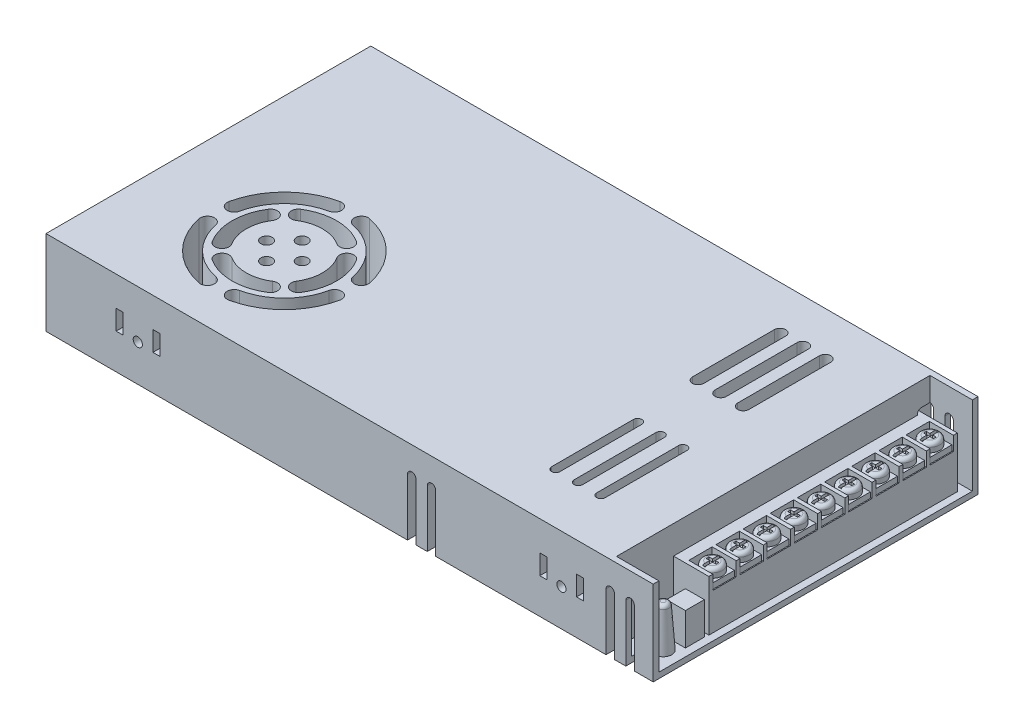
SolidWorks part; units mm, degrees
material "aluminio"
ref_plane "Alzado" through (0, 0, 0) normal (0, 0, 1) x (1, 0, 0)
ref_plane "Planta" through (0, 0, 0) normal (0, 1, 0) x (1, 0, 0)
ref_plane "Vista lateral" through (0, 0, 0) normal (1, 0, 0) x (0, 0, -1)
sketch "Croquis1" plane through (0, 0, 0) normal (0, 1, 0) x (1, 0, 0)
  line L1 (0, 0) -> (215, 0)
  line L2 (0, 0) -> (0, 115)
  line L3 (0, 115) -> (215, 115)
  line L4 (215, 0) -> (215, 115)
  dimension "D1" = 215
  dimension "D2" = 115
extrude "Saliente-Extruir1" add sketch "Croquis1" along normal blind 30
sketch "Croquis2" plane through (0, 30, 0) normal (0, 1, 0) x (1, 0, 0)
  line L0 (215, 0) -> (215, 115) construction
  line L1 (215, 113) -> (200, 113)
  line L2 (215, 113) -> (215, 2)
  line L3 (215, 2) -> (200, 2)
  line L4 (200, 113) -> (200, 2)
  line L5 (215, 115) -> (0, 115) construction
  line L6 (0, 115) -> (0, 0) construction
  line L7 (0, 0) -> (215, 0) construction
  dimension "D1" = 2
  dimension "D2" = 2
  dimension "D3" = 200
extrude "Cortar-Extruir1" cut sketch "Croquis2" against normal offset from surface (28 mm away) 2 up to face at (107.5, 0, -57.5)
sketch "Croquis7" plane through (0, 30, 0) normal (0, 1, 0) x (1, 0, 0)
  line L0 (176.4, 99.5) -> (176.4, 70.5) construction
  line L1 (178.4, 99.5) -> (178.4, 70.5)
  line L2 (174.4, 99.5) -> (174.4, 70.5)
  line L3 (200, 113) -> (200, 2) construction
  line L4 (178.5, 47) -> (178.5, 18) construction
  line L5 (180, 47) -> (180, 18)
  line L6 (177, 47) -> (177, 18)
  line L7 (0, 0) -> (215, 0) construction
  line L8 (215, 115) -> (0, 115) construction
  line L9 (168.4, 99.5) -> (168.4, 70.5) construction
  line L10 (170.4, 99.5) -> (170.4, 70.5)
  line L11 (166.4, 99.5) -> (166.4, 70.5)
  line L12 (170.5, 47) -> (170.5, 18) construction
  line L13 (172, 47) -> (172, 18)
  line L14 (169, 47) -> (169, 18)
  line L15 (160.4, 99.5) -> (160.4, 70.5) construction
  line L16 (162.4, 99.5) -> (162.4, 70.5)
  line L17 (158.4, 99.5) -> (158.4, 70.5)
  line L18 (162.5, 47) -> (162.5, 18) construction
  line L19 (164, 47) -> (164, 18)
  line L20 (161, 47) -> (161, 18)
  line L156 (154.5, 47) -> (154.5, 18) construction
  line L157 (156, 47) -> (156, 18)
  line L158 (153, 47) -> (153, 18)
  line L159 (144.4, 99.5) -> (144.4, 70.5) construction
  line L160 (146.4, 99.5) -> (146.4, 70.5)
  line L161 (142.4, 99.5) -> (142.4, 70.5)
  line L162 (146.5, 47) -> (146.5, 18) construction
  line L163 (148, 47) -> (148, 18)
  line L164 (145, 47) -> (145, 18)
  line L165 (152.4, 99.5) -> (152.4, 70.5) construction
  line L166 (154.4, 99.5) -> (154.4, 70.5)
  line L167 (150.4, 99.5) -> (150.4, 70.5)
  line L168 (154.5, 47) -> (154.5, 18) construction
  line L169 (156, 47) -> (156, 18)
  line L170 (153, 47) -> (153, 18)
  line L171 (144.4, 99.5) -> (144.4, 70.5) construction
  line L172 (146.4, 99.5) -> (146.4, 70.5)
  line L173 (142.4, 99.5) -> (142.4, 70.5)
  line L174 (146.5, 47) -> (146.5, 18) construction
  line L175 (148, 47) -> (148, 18)
  line L176 (145, 47) -> (145, 18)
  line L177 (152.4, 99.5) -> (152.4, 70.5) construction
  line L178 (154.4, 99.5) -> (154.4, 70.5)
  line L179 (150.4, 99.5) -> (150.4, 70.5)
  arc A0 (178.4, 99.5) -> (174.4, 99.5) centre (176.4, 99.5) ccw
  arc A1 (174.4, 70.5) -> (178.4, 70.5) centre (176.4, 70.5) ccw
  arc A2 (180, 47) -> (177, 47) centre (178.5, 47) ccw
  arc A3 (177, 18) -> (180, 18) centre (178.5, 18) ccw
  arc A4 (170.4, 99.5) -> (166.4, 99.5) centre (168.4, 99.5) ccw
  arc A5 (166.4, 70.5) -> (170.4, 70.5) centre (168.4, 70.5) ccw
  arc A6 (172, 47) -> (169, 47) centre (170.5, 47) ccw
  arc A7 (169, 18) -> (172, 18) centre (170.5, 18) ccw
  arc A8 (162.4, 99.5) -> (158.4, 99.5) centre (160.4, 99.5) ccw
  arc A9 (158.4, 70.5) -> (162.4, 70.5) centre (160.4, 70.5) ccw
  arc A10 (164, 47) -> (161, 47) centre (162.5, 47) ccw
  arc A11 (161, 18) -> (164, 18) centre (162.5, 18) ccw
  arc A110 (156, 47) -> (153, 47) centre (154.5, 47) ccw
  arc A111 (153, 18) -> (156, 18) centre (154.5, 18) ccw
  arc A112 (146.4, 99.5) -> (142.4, 99.5) centre (144.4, 99.5) ccw
  arc A113 (142.4, 70.5) -> (146.4, 70.5) centre (144.4, 70.5) ccw
  arc A114 (148, 47) -> (145, 47) centre (146.5, 47) ccw
  arc A115 (145, 18) -> (148, 18) centre (146.5, 18) ccw
  arc A116 (154.4, 99.5) -> (150.4, 99.5) centre (152.4, 99.5) ccw
  arc A117 (150.4, 70.5) -> (154.4, 70.5) centre (152.4, 70.5) ccw
  point P2 (176.4, 85)
  point P11 (178.5, 32.5)
  point P16 (178.5, 16.5)
  point P17 (176.4, 101.5)
  point P25 (168.4, 85)
  point P32 (170.5, 32.5)
  point P39 (160.4, 85)
  point P46 (162.5, 32.5)
  point P53 (154.5412, 34.5)
  point P60 (147.5412, 79.6)
  point P67 (147.5412, 34.5)
  point P80 (154.5412, 79.6)
  point P87 (154.5412, 34.5)
  point P94 (147.5412, 79.6)
  point P101 (147.5412, 34.5)
  point P108 (154.5412, 79.6)
  point P115 (154.5412, 34.5)
  point P122 (147.5412, 79.6)
  point P129 (147.5412, 34.5)
  point P136 (154.5412, 79.6)
  point P143 (154.5412, 34.5)
  point P150 (147.5412, 79.6)
  point P157 (147.5412, 34.5)
  point P164 (154.5412, 79.6)
  point P171 (157.5, 34.5)
  point P178 (150.5, 79.6)
  point P185 (150.5, 34.5)
  point P192 (157.5, 79.6)
  point P199 (157.5, 34.5)
  point P206 (150.5, 79.6)
  point P213 (150.5, 34.5)
  point P220 (157.5, 79.6)
  point P227 (157.5, 34.5)
  point P234 (150.5, 79.6)
  point P241 (150.5, 34.5)
  point P248 (157.5, 79.6)
  point P255 (157.5, 34.5)
  point P262 (150.5, 79.6)
  point P269 (150.5, 34.5)
  point P276 (157.5, 79.6)
  point P283 (157.5, 34.5)
  point P290 (150.5, 79.6)
  point P297 (150.5, 34.5)
  point P304 (157.5, 79.6)
  point P311 (157.5, 34.5)
  point P318 (150.5, 79.6)
  point P325 (150.5, 34.5)
  point P332 (157.5, 79.6)
  point P339 (154.5, 32.5)
  point P346 (144.4, 85)
  point P353 (146.5, 32.5)
  point P360 (152.4, 85)
  point P367 (154.5, 32.5)
  point P374 (144.4, 85)
  point P381 (146.5, 32.5)
  point P388 (152.4, 85)
  point P395 (154.5, 32.5)
  point P402 (144.4, 85)
  point P409 (146.5, 32.5)
  point P416 (152.4, 85)
  dimension "D1" = 21.6
  dimension "D2" = 16.5
  dimension "D5" = 20
  dimension "D6" = 1.5
  dimension "D3" = 13.5
  dimension "D4" = 20
  dimension "D8" = 4
  dimension "D9" = 33
  dimension "D7" = 5
sketch "Croquis5" plane through (0, 0, -115) normal (0, 0, -1) x (-1, 0, 0)
  line L0 (0, 30) -> (0, 0) construction
  line L2 (-215, 30) -> (-215, 0) construction
  line L3 (-215, 30) -> (0, 30) construction
  circle A0 centre (-182.5, 13) radius 1.625
  circle A1 centre (-32.5, 13) radius 1.625
  dimension "D1" = 3.25
  dimension "D2" = 3.25
  dimension "D4" = 17
  dimension "D5" = 17
  dimension "D3" = 32.5
  dimension "D6" = 32.5
extrude "Cortar-Extruir3" cut sketch "Croquis5" against normal through all
cosmetic thread "Rosca cosmética1" parameters "D2"=4
cosmetic thread "Rosca cosmética2" parameters "D2"=4
extrude "Cortar-Extruir5" cut sketch "Croquis7" against normal offset from surface (28 mm away) 2 up to face at (107.5, 0, -57.5)
sketch "Croquis10" plane through (0, 0, -115) normal (0, 0, -1) x (-1, 0, 0)
  line L0 (0, 30) -> (0, 0) construction
  line L1 (-24.85, 12.5) -> (-27.35, 12.5)
  line L2 (-24.85, 12.5) -> (-24.85, 19.5)
  line L3 (-24.85, 19.5) -> (-27.35, 19.5)
  line L4 (-27.35, 12.5) -> (-27.35, 19.5)
  line L5 (-37.85, 12.5) -> (-40.35, 12.5)
  line L6 (-37.85, 12.5) -> (-37.85, 19.5)
  line L7 (-37.85, 19.5) -> (-40.35, 19.5)
  line L8 (-40.35, 12.5) -> (-40.35, 19.5)
  line L9 (-215, 0) -> (0, 0) construction
  line L10 (-174.85, 12.5) -> (-177.35, 12.5)
  line L11 (-174.85, 12.5) -> (-174.85, 19.5)
  line L12 (-174.85, 19.5) -> (-177.35, 19.5)
  line L13 (-177.35, 12.5) -> (-177.35, 19.5)
  line L14 (-187.85, 12.5) -> (-190.35, 12.5)
  line L15 (-187.85, 12.5) -> (-187.85, 19.5)
  line L16 (-187.85, 19.5) -> (-190.35, 19.5)
  line L17 (-190.35, 12.5) -> (-190.35, 19.5)
  dimension "D1" = 2.5
  dimension "D2" = 2.5
  dimension "D3" = 7
  dimension "D4" = 7
  dimension "D5" = 10.5
  dimension "D6" = 24.85
  dimension "D7" = 12.5
  dimension "D8" = 12.5
  dimension "D10" = 134.5
  dimension "D11" = 12.5
  dimension "D9" = 2
extrude "Cortar-Extruir8 (no confirmat)" cut sketch "Croquis10" against normal through all
sketch "Croquis11" plane through (0, 0, 0) normal (0, 1, 0) x (1, 0, 0)
  line L0 (215, 2) -> (215, 113) construction
  line L1 (212.5, 110.2) -> (196.5, 110.2)
  line L2 (212.5, 110.2) -> (212.5, 22.2)
  line L3 (212.5, 22.2) -> (196.5, 22.2)
  line L4 (196.5, 110.2) -> (196.5, 22.2)
  line L5 (215, 113) -> (200, 113) construction
  line L6 (200, 2) -> (215, 2) construction
  dimension "D1" = 20.2
  dimension "D2" = 16
  dimension "D3" = 2.5
  dimension "D4" = 2.8
extrude "Saliente-Extruir2" add sketch "Croquis11" along normal blind 20 separate body
sketch "Croquis12" plane through (212.5, 0, 0) normal (1, 0, 0) x (0, 0, -1)
  line L0 (22.2, 20) -> (110.2, 20) construction
  line L1 (23.6, 20) -> (31.8667, 20)
  line L2 (23.6, 20) -> (23.6, 15)
  line L3 (23.6, 15) -> (31.8667, 15)
  line L4 (31.8667, 20) -> (31.8667, 15)
  line L6 (41.4833, 20) -> (41.4833, 15)
  line L7 (33.2167, 15) -> (41.4833, 15)
  line L8 (33.2167, 20) -> (33.2167, 15)
  line L9 (33.2167, 20) -> (41.4833, 20)
  line L10 (51.1, 20) -> (51.1, 15)
  line L11 (42.8333, 15) -> (51.1, 15)
  line L12 (42.8333, 20) -> (42.8333, 15)
  line L13 (42.8333, 20) -> (51.1, 20)
  line L14 (60.7167, 20) -> (60.7167, 15)
  line L15 (52.45, 15) -> (60.7167, 15)
  line L16 (52.45, 20) -> (52.45, 15)
  line L17 (52.45, 20) -> (60.7167, 20)
  line L18 (70.3333, 20) -> (70.3333, 15)
  line L19 (62.0667, 15) -> (70.3333, 15)
  line L20 (62.0667, 20) -> (62.0667, 15)
  line L21 (62.0667, 20) -> (70.3333, 20)
  line L22 (79.95, 20) -> (79.95, 15)
  line L23 (71.6833, 15) -> (79.95, 15)
  line L24 (71.6833, 20) -> (71.6833, 15)
  line L25 (71.6833, 20) -> (79.95, 20)
  line L26 (89.5667, 20) -> (89.5667, 15)
  line L27 (81.3, 15) -> (89.5667, 15)
  line L28 (81.3, 20) -> (81.3, 15)
  line L29 (81.3, 20) -> (89.5667, 20)
  line L30 (99.1833, 20) -> (99.1833, 15)
  line L31 (90.9167, 15) -> (99.1833, 15)
  line L32 (90.9167, 20) -> (90.9167, 15)
  line L33 (90.9167, 20) -> (99.1833, 20)
  line L34 (108.8, 20) -> (108.8, 15)
  line L35 (100.5333, 15) -> (108.8, 15)
  line L36 (100.5333, 20) -> (100.5333, 15)
  line L37 (100.5333, 20) -> (108.8, 20)
  line L39 (110.2, 20) -> (110.2, 0) construction
  line L40 (22.2, 20) -> (22.2, 0) construction
  dimension "D1" = 1.4
  dimension "D2" = 5
  dimension "D3" = 1.4
  dimension "D5" = 1.35
  dimension "D4" = 9
extrude "Cortar-Extruir11" cut sketch "Croquis12" against normal blind 8.5
sketch "Croquis17" plane through (0, 0, -115) normal (0, 0, -1) x (-1, 0, 0)
  line L0 (-136.5, 20.2) -> (-136.5, 0) construction
  line L1 (-135, 20.2) -> (-135, 0)
  line L2 (-138, 20.2) -> (-138, 0)
  line L3 (-215, 0) -> (0, 0) construction
  line L4 (-129.5, 20.2) -> (-129.5, 0) construction
  line L5 (-215, 30) -> (-215, 0) construction
  line L6 (-128, 20.2) -> (-128, 0)
  line L7 (-131, 20.2) -> (-131, 0)
  line L8 (-199.8, 0) -> (-199.8, 20.2) construction
  line L9 (-201.3, 0) -> (-201.3, 20.2)
  line L10 (-198.3, 0) -> (-198.3, 20.2)
  line L11 (-206.8, 0) -> (-206.8, 20.2) construction
  line L12 (-208.3, 0) -> (-208.3, 20.2)
  line L13 (-205.3, 0) -> (-205.3, 20.2)
  arc A0 (-135, 20.2) -> (-138, 20.2) centre (-136.5, 20.2) ccw
  arc A1 (-138, 0) -> (-135, 0) centre (-136.5, 0) ccw
  arc A2 (-128, 20.2) -> (-131, 20.2) centre (-129.5, 20.2) ccw
  arc A3 (-131, 0) -> (-128, 0) centre (-129.5, 0) ccw
  arc A4 (-201.3, 0) -> (-198.3, 0) centre (-199.8, 0) ccw
  arc A5 (-198.3, 20.2) -> (-201.3, 20.2) centre (-199.8, 20.2) ccw
  arc A6 (-208.3, 0) -> (-205.3, 0) centre (-206.8, 0) ccw
  arc A7 (-205.3, 20.2) -> (-208.3, 20.2) centre (-206.8, 20.2) ccw
  point P2 (-136.5, 10.1)
  point P7 (-136.5, 21.7)
  point P8 (-136.5, -1.5)
  point P16 (-129.5, 10.1)
  point P21 (-129.5, 21.7)
  point P22 (-129.5, -1.5)
  point P24 (-199.8, 10.1)
  point P31 (-206.8, 10.1)
  dimension "D2" = 1.5
  dimension "D1" = 21.7
  dimension "D3" = 2
  dimension "D4" = 77
  dimension "D6" = 6.7
  dimension "D5" = 4
  dimension "D7" = 4
extrude "Cortar-Extruir15" cut sketch "Croquis17" against normal blind 6.4
extrude "Cut-Extrude2" cut sketch "Croquis17<2>" against normal blind 10 from offset 110 offset against normal yes
sketch "Croquis17<2>" plane through (0, 0, -115) normal (0, 0, -1) x (-1, 0, 0) same geometry as "Croquis17"
fillet "Redondeo3" radius 1.3 22 edges at (128, 10.1, -108.6) (129.5, 21.7, -108.6) (136.5, 21.7, -108.6) (198.8126, 21.3292, -108.6) (131, 10.1, -108.6) (135, 10.1, -108.6) (138, 10.1, -108.6) (198.3, 10.1, -108.6) (201.3, 1, -108.6) (205.3, 1, -108.6) (208.3, 1, -108.6) (198.8126, 21.3292, -5) (128, 10.1, -5) (129.5, 21.7, -5) (135, 10.1, -5) (136.5, 21.7, -5) (205.3, 1, -5) (198.3, 10.1, -5) (208.3, 1, -5) (201.3, 1, -5) (131, 10.1, -5) (138, 10.1, -5)
sketch "Croquis18" plane through (0, 30, 0) normal (0, 1, 0) x (1, 0, 0)
  line L0 (33.9854, 45.4648) -> (33.9854, 28.3352) construction
  line L1 (70.0042, 41.65) -> (70.0042, 32.15) construction
  line L2 (0, 115) -> (0, 0) construction
  line L3 (0, 0) -> (215, 0) construction
  arc A0 (42.2337, 61.8503) -> (22.5497, 42.1663) centre (47.5, 36.9) ccw
  arc A1 (43.2663, 56.9581) -> (27.4419, 41.1337) centre (47.5, 36.9) ccw
  arc A2 (22.5497, 42.1663) -> (27.4419, 41.1337) centre (24.9958, 41.65) ccw
  arc A3 (43.2663, 56.9581) -> (42.2337, 61.8503) centre (42.75, 59.4042) ccw
  arc A4 (67.5581, 41.1337) -> (51.7337, 56.9581) centre (47.5, 36.9) ccw
  arc A5 (52.7663, 61.8503) -> (51.7337, 56.9581) centre (52.25, 59.4042) ccw
  arc A6 (72.4503, 42.1663) -> (52.7663, 61.8503) centre (47.5, 36.9) ccw
  arc A7 (67.5581, 41.1337) -> (72.4503, 42.1663) centre (70.0042, 41.65) ccw
  arc A8 (51.7337, 16.8419) -> (67.5581, 32.6663) centre (47.5, 36.9) ccw
  arc A9 (72.4503, 31.6337) -> (67.5581, 32.6663) centre (70.0042, 32.15) ccw
  arc A10 (52.7663, 11.9497) -> (72.4503, 31.6337) centre (47.5, 36.9) ccw
  arc A11 (51.7337, 16.8419) -> (52.7663, 11.9497) centre (52.25, 14.3958) ccw
  arc A12 (27.4419, 32.6663) -> (43.2663, 16.8419) centre (47.5, 36.9) ccw
  arc A13 (42.2337, 11.9497) -> (43.2663, 16.8419) centre (42.75, 14.3958) ccw
  arc A14 (22.5497, 31.6337) -> (42.2337, 11.9497) centre (47.5, 36.9) ccw
  arc A15 (27.4419, 32.6663) -> (22.5497, 31.6337) centre (24.9958, 32.15) ccw
  arc A16 (33.9854, 28.3352) -> (33.9854, 45.4648) centre (47.5, 36.9) cw construction
  arc A17 (31.8738, 46.8031) -> (31.8738, 26.9969) centre (47.5, 36.9) ccw
  arc A18 (36.0971, 44.1266) -> (36.0971, 29.6734) centre (47.5, 36.9) ccw
  arc A19 (36.0971, 44.1266) -> (31.8738, 46.8031) centre (33.9854, 45.4648) ccw
  arc A20 (31.8738, 26.9969) -> (36.0971, 29.6734) centre (33.9854, 28.3352) ccw
  arc A21 (38.9352, 50.4146) -> (56.0648, 50.4146) centre (47.5, 36.9) cw construction
  arc A22 (57.4031, 52.5262) -> (37.5969, 52.5262) centre (47.5, 36.9) ccw
  arc A23 (54.7266, 48.3029) -> (40.2734, 48.3029) centre (47.5, 36.9) ccw
  arc A24 (54.7266, 48.3029) -> (57.4031, 52.5262) centre (56.0648, 50.4146) ccw
  arc A25 (37.5969, 52.5262) -> (40.2734, 48.3029) centre (38.9352, 50.4146) ccw
  arc A26 (61.0146, 45.4648) -> (61.0146, 28.3352) centre (47.5, 36.9) cw construction
  arc A27 (63.1262, 26.9969) -> (63.1262, 46.8031) centre (47.5, 36.9) ccw
  arc A28 (58.9029, 29.6734) -> (58.9029, 44.1266) centre (47.5, 36.9) ccw
  arc A29 (58.9029, 29.6734) -> (63.1262, 26.9969) centre (61.0146, 28.3352) ccw
  arc A30 (63.1262, 46.8031) -> (58.9029, 44.1266) centre (61.0146, 45.4648) ccw
  arc A31 (38.9352, 23.3854) -> (56.0648, 23.3854) centre (47.5, 36.9) ccw construction
  arc A32 (37.5969, 21.2738) -> (57.4031, 21.2738) centre (47.5, 36.9) ccw
  arc A33 (40.2734, 25.4971) -> (54.7266, 25.4971) centre (47.5, 36.9) ccw
  arc A34 (40.2734, 25.4971) -> (37.5969, 21.2738) centre (38.9352, 23.3854) ccw
  arc A35 (57.4031, 21.2738) -> (54.7266, 25.4971) centre (56.0648, 23.3854) ccw
  circle A36 centre (47.5, 36.9) radius 6.3 construction
  circle A37 centre (41.2, 36.9) radius 2
  circle A38 centre (47.5, 43.2) radius 2
  circle A39 centre (53.8, 36.9) radius 2
  circle A40 centre (47.5, 30.6) radius 2
  point P2 (24.6901, 48.3)
  point P33 (31.5, 36.9)
  point P42 (47.5, 52.9)
  point P45 (47.5, 36.9)
  point P48 (63.5, 36.9)
  point P56 (47.5, 20.9)
  dimension "D1" = 51
  dimension "D2" = 41
  dimension "D5" = 5
  dimension "D6" = 4.5
  dimension "D7" = 5
  dimension "D8" = 6.65
  dimension "D10" = 5
  dimension "D11" = 37
  dimension "D12" = 2
  dimension "D13" = 4
  dimension "D14" = 16.6
  dimension "D3" = 47.5
  dimension "D4" = 36.9
  dimension "D9" = 4
extrude "Cortar-Extruir17" cut sketch "Croquis18" against normal offset from surface (28 mm away) 2 up to face at (163.4846, 0, -57.0692)
sketch "Croquis28" plane through (0, 0, 0) normal (0, -1, 0) x (1, 0, 0)
  line L0 (212.5, -22.2) -> (212.5, -110.2) construction
  line L2 (208.3, 0) -> (215, 0) construction
  line L7 (30, -32.5) -> (180, -32.5) construction
  line L8 (30, -32.5) -> (30, -82.5) construction
  line L9 (30, -82.5) -> (180, -82.5) construction
  line L10 (180, -32.5) -> (180, -82.5) construction
  circle A0 centre (30, -32.5) radius 1.625
  circle A1 centre (30, -82.5) radius 1.625
  circle A2 centre (180, -32.5) radius 1.625
  circle A3 centre (180, -82.5) radius 1.625
  dimension "D1" = 3.25
  dimension "D3" = 150
  dimension "D4" = 50
  dimension "D5" = 32.5
  dimension "D6" = 32.5
extrude "Cortar-Extruir23" cut sketch "Croquis28" against normal blind 2
cosmetic thread "Rosca cosmética3" parameters "D2"=4
cosmetic thread "Rosca cosmética4" parameters "D2"=4
cosmetic thread "Rosca cosmética5" parameters "D2"=4
cosmetic thread "Rosca cosmética6" parameters "D2"=4
sketch "Sketch1" plane through (0, 30, 0) normal (0, 1, 0) x (1, 0, 0)
  line L0 (187.9485, 115) -> (187.9485, 1.484) construction
  line L3 (215, 115) -> (0, 115) construction
  text T0 "<b>   |POWER AC|       POWER DC      |</b>" font "Century Gothic" height in points 16
extrude "Cut-Extrude3" [suppressed] cut sketch "Sketch1" against normal blind 1
sketch "Croquis29" plane through (0, 15, 0) normal (0, 1, 0) x (1, 0, 0)
  line L0 (204, 23.6) -> (212.5, 31.8667) construction
  circle A0 centre (208.25, 27.7333) radius 3.5
  dimension "D1" = 7
extrude "Saliente-Extruir3" add sketch "Croquis29" along normal blind 5 separate body
fillet "Redondeo4" radius 1.3 1 edges at (208.25, 20, -24.2333)
sketch "Croquis30" plane through (0, 20, 0) normal (0, 1, 0) x (1, 0, 0)
  line L0 (206.05, 27.7333) -> (210.45, 27.7333) construction
  line L1 (207.75, 30.7333) -> (208.75, 30.7333)
  line L2 (207.75, 30.7333) -> (207.75, 24.7333)
  line L3 (207.75, 24.7333) -> (208.75, 24.7333)
  line L4 (208.75, 30.7333) -> (208.75, 24.7333)
  line L5 (208.25, 30.7333) -> (208.25, 24.7333) construction
  circle A0 centre (208.25, 27.7333) radius 2.2 construction
  point P11 (208.25, 27.7333)
  dimension "D1" = 6
  dimension "D2" = 1
extrude "Cortar-Extruir24" cut sketch "Croquis30" against normal blind 1
sketch "Croquis31" plane through (0, 20, 0) normal (0, 1, 0) x (1, 0, 0)
  line L0 (208.25, 30.7333) -> (208.25, 24.7333) construction
  line L1 (206.5, 28.2333) -> (210, 28.2333)
  line L2 (206.5, 28.2333) -> (206.5, 27.2333)
  line L3 (206.5, 27.2333) -> (210, 27.2333)
  line L4 (210, 28.2333) -> (210, 27.2333)
  line L5 (208.75, 24.7333) -> (207.75, 24.7333) construction
  line L6 (207.75, 30.7333) -> (208.75, 30.7333) construction
  line L7 (206.5, 27.7333) -> (210, 27.7333) construction
  point P12 (208.25, 27.7333)
  dimension "D1" = 3.5
extrude "Cortar-Extruir25" cut sketch "Croquis31" against normal up to surface (1 mm away) up to face at (208.25, 19, -27.7333)
sketch "Croquis32" plane through (0, 15, 0) normal (0, 1, 0) x (1, 0, 0)
  line L0 (204.35, 23.8333) -> (212.15, 31.6333) construction
  line L1 (204.35, 31.6333) -> (212.15, 31.6333)
  line L2 (204.35, 31.6333) -> (204.35, 23.8333)
  line L3 (204.35, 23.8333) -> (212.15, 23.8333)
  line L4 (212.15, 31.6333) -> (212.15, 23.8333)
  arc A0 (208.75, 25.5909) -> (208.75, 29.8758) centre (208.25, 27.7333) ccw construction
  point P4 (208.25, 27.7333)
  dimension "D1" = 7.8
extrude "Saliente-Extruir4" add sketch "Croquis32" along normal blind 2
sketch "Croquis33" plane through (0, 15, 0) normal (0, 1, 0) x (1, 0, 0)
  line L0 (204, 46.9667) -> (204, 56.5833) construction
  line L1 (204, 42.8333) -> (204, 51.1) construction
  line L2 (204, 52.45) -> (204, 60.7167) construction
  dimension "D1" = 9.6167
pattern_linear "MatrizL1" count 9 spacing 9.62 along (0, 0, -1) of bodies 132
sketch "Croquis34" plane through (0, 2, 0) normal (0, 1, 0) x (1, 0, 0)
  line L0 (215, 2) -> (215, 113) construction
  line L1 (205.6, 14.1) -> (212.3, 14.1)
  line L2 (205.6, 14.1) -> (205.6, 20.8)
  line L3 (205.6, 20.8) -> (212.3, 20.8)
  line L4 (212.3, 14.1) -> (212.3, 20.8)
  line L5 (196.5, 22.2) -> (212.5, 22.2) construction
  dimension "D1" = 6.7
  dimension "D2" = 2.7
  dimension "D3" = 1.4
extrude "Saliente-Extruir5" add sketch "Croquis34" along normal blind 11.5 separate body
sketch "Croquis35" plane through (0, 2, 0) normal (0, 1, 0) x (1, 0, 0)
  line L0 (208.95, 9.6) -> (208.95, 14.1) construction
  line L1 (205.6, 14.1) -> (212.3, 14.1) construction
  circle A0 centre (208.95, 9.6) radius 3
  dimension "D2" = 6
  dimension "D1" = 4.5
extrude "Saliente-Extruir6" add sketch "Croquis35" along normal blind 15 draft 4 separate body
fillet "Redondeo5" radius 1.3 1 edges at (208.95, 17, -7.6489)
